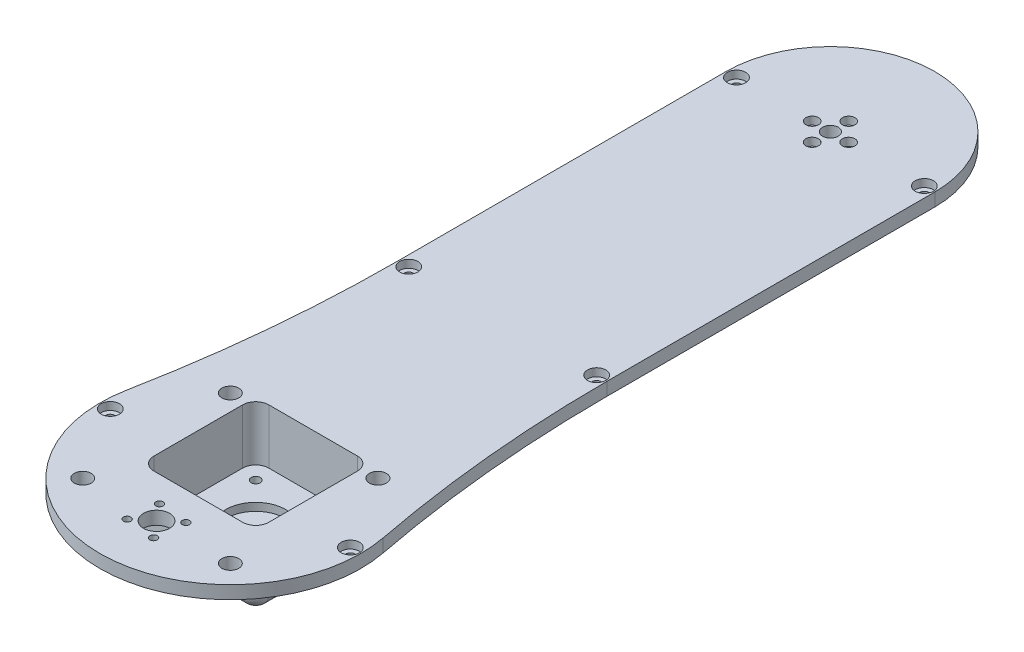
SolidWorks part; units mm, degrees
ref_plane "前视基准面" through (0, 0, 0) normal (0, 0, 1) x (1, 0, 0)
ref_plane "上视基准面" through (0, 0, 0) normal (0, 1, 0) x (1, 0, 0)
ref_plane "右视基准面" through (0, 0, 0) normal (1, 0, 0) x (0, 0, -1)
other "Configuration Table"
sketch "草图1" plane through (0, 0, 0) normal (0, 1, 0) x (1, 0, 0)
  line L2 (-40, 104.4031) -> (-40, 230)
  line L4 (40, 230) -> (40, 104.4031)
  arc A0 (-49.0909, 9.4912) -> (49.0909, 9.4912) centre (0, 0) ccw
  arc A2 (49.0909, 9.4912) -> (40, 104.4031) centre (540, 104.4031) cw
  arc A3 (-40, 104.4031) -> (-49.0909, 9.4912) centre (-540, 104.4031) cw
  arc A4 (40, 230) -> (-40, 230) centre (0, 230) ccw construction
  arc A5 (40, 230) -> (-40, 230) centre (0, 230) ccw
  dimension "D1" = 100
  dimension "D2" = 500
extrude "凸台-拉伸1" add sketch "草图1" along normal blind 5
sketch "草图2" plane through (0, 5, 0) normal (0, 1, 0) x (1, 0, 0)
  circle A0 centre (28.2843, 28.2843) radius 3.25
  circle A1 centre (28.2843, -28.2843) radius 3.25
  circle A2 centre (-28.2843, -28.2843) radius 3.25
  circle A3 centre (-28.2843, 28.2843) radius 3.25
  point P12 (0, 0)
  dimension "D1" = 6.5
  dimension "D2" = 4
extrude "切除-拉伸1" cut sketch "草图2" against normal blind 5
sketch "草图3" plane through (0, 5, 0) normal (0, 1, 0) x (1, 0, 0)
  circle A0 centre (0, -28.2843) radius 5
  dimension "D1" = 10
extrude "切除-拉伸2" cut sketch "草图3" against normal blind 5
sketch "草图4" plane through (0, 0, 0) normal (0, -1, 0) x (1, 0, 0)
  circle A0 centre (5.0686, 34.4738) radius 1.4
  circle A1 centre (6.1895, 23.2157) radius 1.4
  circle A2 centre (-5.0686, 22.0948) radius 1.4
  circle A3 centre (-6.1895, 33.3528) radius 1.4
  point P12 (0, 28.2843)
  dimension "D1" = 2.8
  dimension "D2" = 4
extrude "切除-拉伸3" cut sketch "草图4" against normal blind 5
sketch "草图10" plane through (0, 0, 0) normal (0, -1, 0) x (1, 0, 0)
  line L0 (0, 0) -> (0, -50000) construction
  circle A0 centre (46, 0) radius 1.75
  circle A1 centre (36, -104.4031) radius 1.75
  circle A2 centre (36, -230) radius 1.75
  circle A3 centre (-36, -230) radius 1.75
  circle A4 centre (-36, -104.4031) radius 1.75
  circle A5 centre (-46, 0) radius 1.75
  dimension "D1" = 3.5
  dimension "D2" = 3.5
  dimension "D3" = 3.5
extrude "切除-拉伸8" cut sketch "草图10" against normal blind 45
sketch "草图11" plane through (0, 5, 0) normal (0, 1, 0) x (1, 0, 0)
  line L0 (0, 270) -> (0, -49730) construction
  circle A0 centre (-36, 230) radius 3.5
  circle A1 centre (-36, 104.4031) radius 3.5
  circle A2 centre (-46, 0) radius 3.5
  arc A3 (40, 230) -> (-40, 230) centre (0, 230) ccw construction
  circle A4 centre (46, 0) radius 3.5
  circle A5 centre (36, 104.4031) radius 3.5
  circle A6 centre (36, 230) radius 3.5
  point P14 (0, 270)
  dimension "D1" = 7
  dimension "D2" = 7
  dimension "D3" = 7
extrude "切除-拉伸9" cut sketch "草图11" against normal blind 3
sketch "草图12" plane through (0, 5, 0) normal (0, 1, 0) x (1, 0, 0)
  line L0 (0, 0) -> (0, 50000) construction
  line L1 (-22, -12.2643) -> (22, -12.2643)
  line L2 (-22, -12.2643) -> (-22, 31.7357)
  line L3 (-22, 31.7357) -> (22, 31.7357)
  line L4 (22, -12.2643) -> (22, 31.7357)
  line L5 (-22, -12.2643) -> (22, 31.7357) construction
  line L6 (-22, 31.7357) -> (22, -12.2643) construction
  point P0 (0, 9.7357)
  dimension "D1" = 44
  dimension "D2" = 44
  dimension "D3" = 22
extrude "切除-拉伸10" cut sketch "草图12" against normal blind 10
sketch "草图13" plane through (0, 0, 0) normal (0, -1, 0) x (1, 0, 0)
  line L1 (-22, 12.2643) -> (22, 12.2643)
  line L2 (-22, 12.2643) -> (-22, -31.7357)
  line L3 (-22, -31.7357) -> (22, -31.7357)
  line L4 (22, 12.2643) -> (22, -31.7357)
  line L5 (-21, 16.2643) -> (21, 16.2643)
  line L6 (-26, 11.2643) -> (-26, -30.7357)
  line L7 (-21, -35.7357) -> (21, -35.7357)
  line L8 (26, 11.2643) -> (26, -30.7357)
  arc A0 (21, -35.7357) -> (26, -30.7357) centre (21, -30.7357) ccw
  arc A1 (21, 16.2643) -> (26, 11.2643) centre (21, 11.2643) cw
  arc A2 (-26, -30.7357) -> (-21, -35.7357) centre (-21, -30.7357) ccw
  arc A3 (-21, 16.2643) -> (-26, 11.2643) centre (-21, 11.2643) ccw
  dimension "D5" = 5
  dimension "D1" = 4
  dimension "D2" = 4
  dimension "D3" = 4
  dimension "D4" = 4
extrude "凸台-拉伸2" add sketch "草图13" along normal blind 16
ref_plane "基准面1" through (22, -16, 12.2643) normal (-1, 0, 0) x (0, 0, 1)
sketch "草图15" plane through (0, -16, 0) normal (0, -1, 0) x (1, 0, 0)
  line L24 (26, -30.7357) -> (26, 11.2643)
  line L25 (-21, -35.7357) -> (21, -35.7357)
  line L26 (-26, 11.2643) -> (-26, -30.7357)
  line L27 (21, 16.2643) -> (-21, 16.2643)
  line L28 (26, -30.7357) -> (26, 11.2643)
  line L29 (-21, -35.7357) -> (21, -35.7357)
  line L30 (-26, 11.2643) -> (-26, -30.7357)
  line L31 (21, 16.2643) -> (-21, 16.2643)
  arc A20 (26, 11.2643) -> (21, 16.2643) centre (21, 11.2643) ccw
  arc A21 (21, -35.7357) -> (26, -30.7357) centre (21, -30.7357) ccw
  arc A22 (-26, -30.7357) -> (-21, -35.7357) centre (-21, -30.7357) ccw
  arc A23 (-21, 16.2643) -> (-26, 11.2643) centre (-21, 11.2643) ccw
  arc A24 (26, 11.2643) -> (21, 16.2643) centre (21, 11.2643) ccw
  arc A25 (21, -35.7357) -> (26, -30.7357) centre (21, -30.7357) ccw
  arc A26 (-26, -30.7357) -> (-21, -35.7357) centre (-21, -30.7357) ccw
  arc A27 (-21, 16.2643) -> (-26, 11.2643) centre (-21, 11.2643) ccw
  dimension "D1" = 0
extrude "凸台-拉伸3" add sketch "草图15" along normal blind 4
fillet "圆角1" radius 5 8 edges at (26, -20, -9.7357) (24.5355, -20, -34.2713) (0, -20, -35.7357) (-24.5355, -20, -34.2713) (-26, -20, -9.7357) (-24.5355, -20, 14.7998) (0, -20, 16.2643) (24.5355, -20, 14.7998)
sketch "草图16" plane through (0, -16, 0) normal (0, 1, 0) x (1, 0, 0)
  line L0 (-22, 9.7357) -> (49978, 9.7357) construction
  line L1 (-22, 31.7357) -> (-22, -12.2643) construction
  line L2 (22, -12.2643) -> (22, 31.7357) construction
  circle A0 centre (0, 9.7357) radius 11.5
  point P9 (-22, 9.7357)
  point P12 (22, 9.7357)
  dimension "D1" = 23
extrude "切除-拉伸11" cut sketch "草图16" against normal blind 3
sketch "草图17" plane through (0, -19, 0) normal (0, 1, 0) x (1, 0, 0)
  circle A0 centre (0, 9.7357) radius 3
  dimension "D1" = 6
extrude "切除-拉伸12" cut sketch "草图17" against normal blind 3
fillet "圆角2" radius 5 4 edges at (22, -5.5, 12.2643) (-22, -5.5, 12.2643) (-22, -5.5, -31.7357) (22, -5.5, -31.7357)
sketch "草图18" plane through (0, -16, 0) normal (0, 1, 0) x (1, 0, 0)
  circle A0 centre (-15.494, 25.2297) radius 1.75
  circle A1 centre (15.494, 25.2297) radius 1.75
  circle A2 centre (15.494, -5.7583) radius 1.75
  circle A3 centre (-15.494, -5.7583) radius 1.75
  point P12 (0, 9.7357)
  dimension "D1" = 3.5
  dimension "D2" = 4
extrude "切除-拉伸13" cut sketch "草图18" against normal blind 18
sketch "草图20" plane through (0, 0, 0) normal (0, -1, 0) x (1, 0, 0)
  circle A0 centre (0, -230) radius 3
  dimension "D1" = 6
extrude "切除-拉伸14" cut sketch "草图20" against normal blind 39
sketch "草图21" plane through (0, 0, 0) normal (0, -1, 0) x (1, 0, 0)
  circle A0 centre (0, -230) radius 4.5
  circle A1 centre (0, -230) radius 3
  dimension "D1" = 9
extrude "凸台-拉伸4" add sketch "草图21" along normal blind 20
chamfer "倒角1" distance 10 angle 60 1 edges at (0, 0, -234.5) first distance on face at (0, 0, -111.3105)
sketch "草图22" plane through (0, 5, 0) normal (0, 1, 0) x (1, 0, 0)
  circle A0 centre (7, 229.9832) radius 2.4
  circle A1 centre (0, 230) radius 3 construction
  circle A2 centre (-0.0168, 223) radius 2.4
  circle A3 centre (-7, 230.0168) radius 2.4
  circle A4 centre (0.0168, 237) radius 2.4
  point P13 (0, 230)
  dimension "D1" = 4.8
  dimension "D2" = 7
  dimension "D3" = 4
extrude "切除-拉伸16" cut sketch "草图22" against normal blind 3
